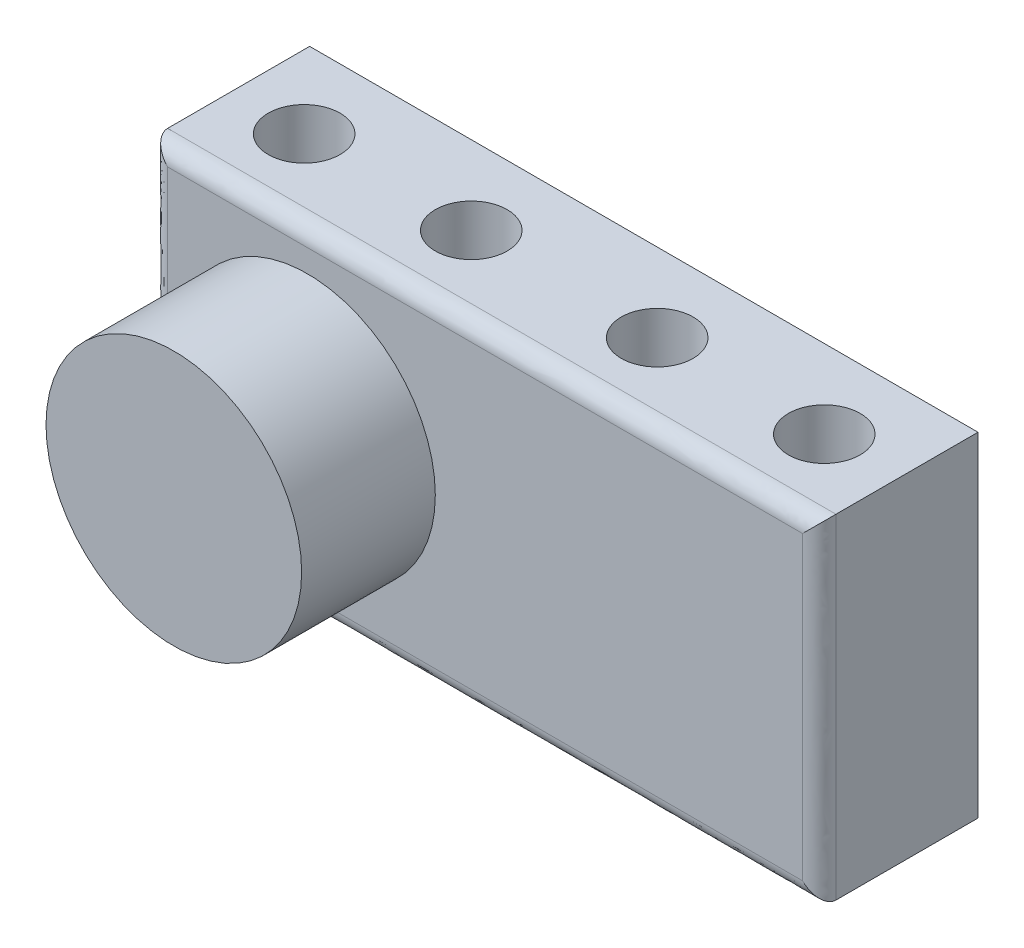
SolidWorks part; units mm, degrees
material "petg 20%"
ref_plane "Front Plane" through (0, 0, 0) normal (0, 0, 1) x (1, 0, 0)
ref_plane "Top Plane" through (0, 0, 0) normal (0, 1, 0) x (1, 0, 0)
ref_plane "Right Plane" through (0, 0, 0) normal (1, 0, 0) x (0, 0, -1)
sketch "Sketch1" plane through (0, 0, 0) normal (0, 0, 1) x (1, 0, 0)
  line L1 (-20, 10) -> (20, 10)
  line L2 (-20, 10) -> (-20, -10)
  line L3 (-20, -10) -> (20, -10)
  line L4 (20, 10) -> (20, -10)
  line L5 (-20, 10) -> (20, -10) construction
  line L6 (-20, -10) -> (20, 10) construction
  point P0 (0, 0)
  dimension "D1" = 40
  dimension "D2" = 20
extrude "Boss-Extrude1" add sketch "Sketch1" along normal blind 9.5
fillet "Fillet1" radius 1 4 edges at (0, -10, 9.5) (20, 0, 9.5) (0, 10, 9.5) (-20, 0, 9.5) first distance on face at (0, -10, 4.75) first distance on face at (20, 0, 4.75) first distance on face at (0, 10, 4.75) first distance on face at (-20, 0, 4.75)
sketch "Sketch4" plane through (0, 0, 9.5) normal (0, 0, 1) x (1, 0, 0)
  circle A0 centre (-10.6286, 0) radius 7.5
  dimension "D1" = 15
extrude "Boss-Extrude2" add sketch "Sketch4" along normal blind 8
sketch "Sketch5" plane through (0, -10, 0) normal (0, -1, 0) x (1, 0, 0)
  line L2 (-18.1286, 17.5) -> (-18.1286, 9.5) construction
  line L3 (-3.1286, 9.5) -> (-3.1286, 17.5) construction
  circle A0 centre (-15.6286, 4.7) radius 2.15
  circle A1 centre (-5.6286, 4.7) radius 2.15
  circle A2 centre (5.5, 4.7) radius 2.15
  circle A3 centre (15.5, 4.7) radius 2.15
  dimension "D1" = 4.3
  dimension "D2" = 4.3
  dimension "D3" = 4.3
  dimension "D4" = 4.3
  dimension "D5" = 2.5
  dimension "D6" = 2.5
  dimension "D7" = 10
extrude "Cut-Extrude1" cut sketch "Sketch5" against normal through all
sketch "Sketch6" plane through (0, 0, 9.5) normal (0, 0, 1) x (1, 0, 0)
  circle A0 centre (-10.6286, 0) radius 7.65
  dimension "D1" = 15.3
extrude "Boss-Extrude3" add sketch "Sketch6" along normal up to surface (8 mm away) up to face at (-3.1286, 0, 17.5)
